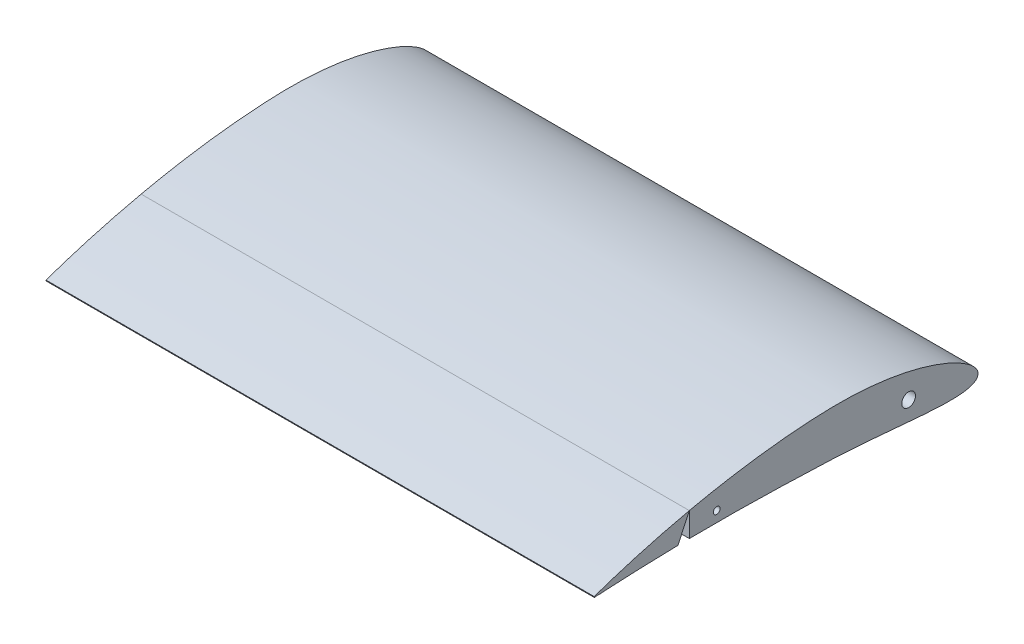
SolidWorks part; units mm, degrees
material "Thornel Mat VMA Foam Core"
ref_plane "Front Plane" through (0, 0, 0) normal (0, 0, 1) x (1, 0, 0)
ref_plane "Top Plane" through (0, 0, 0) normal (0, 1, 0) x (1, 0, 0)
ref_plane "Right Plane" through (0, 0, 0) normal (1, 0, 0) x (0, 0, -1)
curve "Curve1"
  spline degree 3 poles (0, 0.0012, 1.0003) (0, 0.0015, 0.9994) (0, 0.0028, 0.9958) (0, 0.0055, 0.9879) (0, 0.0099, 0.9747) (0, 0.0159, 0.9565) (0, 0.0233, 0.9333) (0, 0.0318, 0.9054) (0, 0.0411, 0.8731) (0, 0.051, 0.8366) (0, 0.0612, 0.7964) (0, 0.0713, 0.7528) (0, 0.0811, 0.7063) (0, 0.0903, 0.6574) (0, 0.0985, 0.6067) (0, 0.1057, 0.5546) (0, 0.1115, 0.5018) (0, 0.1158, 0.4488) (0, 0.1186, 0.3959) (0, 0.1189, 0.3436) (0, 0.1164, 0.2927) (0, 0.1112, 0.2442) (0, 0.1037, 0.1988) (0, 0.0942, 0.157) (0, 0.0831, 0.1194) (0, 0.0711, 0.0865) (0, 0.0584, 0.0585) (0, 0.0457, 0.0357) (0, 0.0334, 0.0184) (0, 0.0218, 0.0064) (0, 0.0108, -0.0005) (0, -0.0003, -0.0011) (0, -0.0092, 0.0055) (0, -0.0148, 0.017) (0, -0.0185, 0.0329) (0, -0.0204, 0.0533) (0, -0.0208, 0.0781) (0, -0.0198, 0.107) (0, -0.0176, 0.1398) (0, -0.0147, 0.176) (0, -0.0111, 0.2153) (0, -0.0074, 0.2574) (0, -0.0037, 0.3019) (0, -0.0005, 0.3484) (0, 0.002, 0.397) (0, 0.0037, 0.4471) (0, 0.0055, 0.4983) (0, 0.0069, 0.5496) (0, 0.0079, 0.6006) (0, 0.0085, 0.6505) (0, 0.0086, 0.699) (0, 0.0083, 0.7455) (0, 0.0076, 0.7894) (0, 0.0065, 0.8302) (0, 0.0053, 0.8675) (0, 0.0039, 0.9007) (0, 0.0027, 0.9296) (0, 0.0013, 0.9539) (0, 0.0006, 0.9727) (0, -0.0011, 0.9872) (0, 0, 0.9944) (0, -0.002, 0.9999) (0, -0.0005, 1) (0, 0, 1) knots 0 0 0 0 0.001372 0.005465 0.012235 0.021602 0.033461 0.047671 0.064081 0.082496 0.102719 0.124527 0.147676 0.171913 0.196978 0.222597 0.248497 0.274385 0.300041 0.32569 0.350525 0.37428 0.396711 0.417577 0.436654 0.453744 0.46868 0.481329 0.491631 0.499616 0.505546 0.510185 0.514824 0.520702 0.528516 0.538466 0.550543 0.564643 0.580638 0.598345 0.617584 0.638174 0.659922 0.682632 0.706121 0.730727 0.7557 0.780732 0.805564 0.829932 0.85357 0.876213 0.89761 0.917519 0.935698 0.951943 0.966047 0.97784 0.987174 0.993932 0.998018 0.999386 1 1 1 1
sketch "Sketch1" plane through (0, 0, 0) normal (1, 0, 0) x (0, 0, -1)
  line L0 (-354.7873, -0.0303) -> (-354.8762, 0.4104)
  line L1 (-354.7873, -0.0303) -> (0.8093, 1.5275) construction
  line L2 (0.8093, 1.5275) -> (0.7921, 5.4415) construction
  spline S1 degree 3 poles (-354.8762, 0.4104) (-354.5599, 0.5194) (-353.2997, 0.9536) (-350.4787, 1.9271) (-345.801, 3.4978) (-336.0241, 6.7216) (-319.6545, 11.7989) (-300.5983, 17.1306) (-282.4229, 21.7243) (-261.1758, 26.6516) (-238.6223, 31.1455) (-208.7748, 36.0048) (-183.9617, 39.0905) (-158.9023, 41.1132) (-140.0967, 42.1114) (-121.5167, 42.2289) (-103.4222, 41.3211) (-86.1884, 39.4787) (-70.0435, 36.8105) (-55.1998, 33.4329) (-41.8434, 29.5109) (-30.1305, 25.2201) (-20.187, 20.7343) (-12.1072, 16.2263) (-5.9269, 11.8553) (-1.6792, 7.7165) (0.7658, 3.7968) (0.9875, -0.1483) (-1.3511, -3.3089) (-5.4508, -5.2881) (-11.0873, -6.5875) (-18.3491, -7.2685) (-27.1638, -7.4049) (-37.4471, -7.0538) (-49.0831, -6.3019) (-61.9524, -5.238) (-75.9299, -3.9839) (-96.4067, -2.1536) (-117.9372, -0.4584) (-140.4848, 0.6745) (-158.2965, 1.2867) (-176.4839, 1.9179) (-200.672, 2.5862) (-224.5411, 2.9791) (-247.8302, 3.0285) (-264.3373, 2.9074) (-279.9331, 2.6564) (-294.438, 2.2829) (-307.6819, 1.8521) (-319.5134, 1.3711) (-329.7674, 0.9129) (-338.3889, 0.4268) (-345.077, 0.1915) (-350.2276, -0.4064) (-352.7802, -0.0354) (-354.7446, -0.7581) (-354.7772, -0.2025) (-354.7873, -0.0303) knots 0 0 0 0 0.001372 0.005465 0.012235 0.021602 0.047671 0.082496 0.102719 0.124527 0.171913 0.196978 0.248497 0.274385 0.300041 0.32569 0.350525 0.37428 0.396711 0.417577 0.436654 0.453744 0.46868 0.481329 0.491631 0.499616 0.505546 0.510185 0.514824 0.520702 0.528516 0.538466 0.550543 0.564643 0.580638 0.598345 0.617584 0.638174 0.682632 0.706121 0.730727 0.7557 0.780732 0.829932 0.85357 0.876213 0.89761 0.917519 0.935698 0.951943 0.966047 0.97784 0.987174 0.993932 0.998018 0.999386 1 1 1 1
  dimension "D1" = 355.6
extrude "Boss-Extrude1" add sketch "Sketch1" along normal blind 254 and the other way blind 254
sketch "Sketch2" plane through (-254, 0, 0) normal (-1, 0, 0) x (0, 0, 1)
  line L0 (266.7, 0) -> (266.7, 78.4574) construction
  line L1 (195.725, 0) -> (-195.725, 0) construction
  line L2 (0, -27.2986) -> (0, 27.2986) construction
  line L3 (266.7, 25.311) -> (266.7, 2.0657)
  line L4 (266.7, 25.311) -> (277.5394, 2.0657)
  line L5 (277.5394, 2.0657) -> (266.7, 2.0657)
  spline S0 degree 3 poles (354.7873, -0.0303) (354.7772, -0.2025) (354.7446, -0.7581) (352.7802, -0.0354) (350.2276, -0.4064) (345.077, 0.1915) (338.3889, 0.4268) (329.7674, 0.9129) (319.5134, 1.3711) (307.6819, 1.8521) (294.438, 2.2829) (279.9331, 2.6564) (264.3373, 2.9074) (247.8302, 3.0285) (224.5411, 2.9791) (200.672, 2.5862) (176.4839, 1.9179) (158.2965, 1.2867) (140.4848, 0.6745) (117.9372, -0.4584) (96.4067, -2.1536) (75.9299, -3.9839) (61.9524, -5.238) (49.0831, -6.3019) (37.4471, -7.0538) (27.1638, -7.4049) (18.3491, -7.2685) (11.0873, -6.5875) (5.4508, -5.2881) (1.3511, -3.3089) (-0.9875, -0.1483) (-0.7658, 3.7968) (1.6792, 7.7165) (5.9269, 11.8553) (12.1072, 16.2263) (20.187, 20.7343) (30.1305, 25.2201) (41.8434, 29.5109) (55.1998, 33.4329) (70.0435, 36.8105) (86.1884, 39.4787) (103.4222, 41.3211) (121.5167, 42.2289) (140.0967, 42.1114) (158.9023, 41.1132) (183.9617, 39.0905) (208.7748, 36.0048) (238.6223, 31.1455) (261.1758, 26.6516) (282.4229, 21.7243) (300.5983, 17.1306) (319.6545, 11.7989) (336.0241, 6.7216) (345.801, 3.4978) (350.4787, 1.9271) (353.2997, 0.9536) (354.5599, 0.5194) (354.8762, 0.4104) knots 0 0 0 0 0.000614 0.001982 0.006068 0.012826 0.02216 0.033953 0.048057 0.064302 0.082481 0.10239 0.123787 0.14643 0.170068 0.219268 0.2443 0.269273 0.293879 0.317368 0.361826 0.382416 0.401655 0.419362 0.435357 0.449457 0.461534 0.471484 0.479298 0.485176 0.489815 0.494454 0.500384 0.508369 0.518671 0.53132 0.546256 0.563346 0.582423 0.603289 0.62572 0.649475 0.67431 0.699959 0.725615 0.751503 0.803022 0.828087 0.875473 0.897281 0.917504 0.952329 0.978398 0.987765 0.994535 0.998628 1 1 1 1 construction
  dimension "D1" = 266.7
  dimension "D2" = 25
extrude "Cut-Extrude1" cut sketch "Sketch2" against normal up to next
sketch "Sketch3" plane through (-254, 0, 0) normal (-1, 0, 0) x (0, 0, 1)
  line L1 (204.4553, 0) -> (-204.4553, 0) construction
  line L2 (0, -44.7467) -> (0, 44.7467) construction
  circle A0 centre (63.5, 12.7) radius 6.35
  dimension "D1" = 12.7
  dimension "D2" = 12.7
  dimension "D3" = 63.5
sketch "Sketch4" plane through (-254, 0, 0) normal (-1, 0, 0) x (0, 0, 1)
  line L0 (195.725, 0) -> (-195.725, 0) construction
  line L1 (0, -27.2986) -> (0, 27.2986) construction
  circle A0 centre (241.3, 12.7) radius 3.175
  dimension "D1" = 6.35
  dimension "D2" = 12.7
  dimension "D3" = 241.3
sketch "Sketch5" plane through (254, 0, 0) normal (1, 0, 0) x (0, 0, -1)
  circle A0 centre (-63.5, 12.7) radius 6.35 construction
  circle A1 centre (-63.5, 12.7) radius 6.35
extrude "Cut-Extrude3" cut sketch "Sketch5" against normal blind 101.6
sketch "Sketch6" plane through (254, 0, 0) normal (1, 0, 0) x (0, 0, -1)
  circle A0 centre (-241.3, 12.7) radius 3.175 construction
  circle A1 centre (-241.3, 12.7) radius 3.175
extrude "Cut-Extrude4" cut sketch "Sketch6" against normal blind 127
